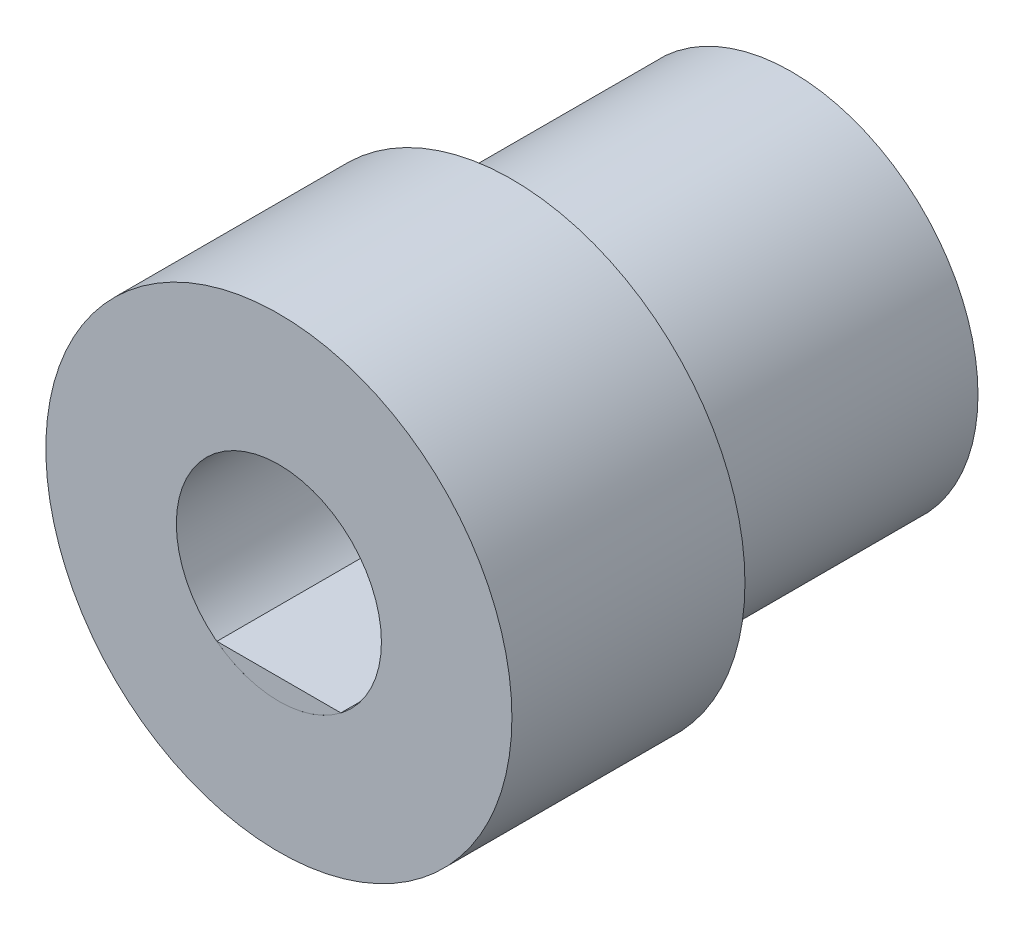
SolidWorks part; units mm, degrees
ref_plane "Plan de face" through (0, 0, 0) normal (0, 0, 1) x (1, 0, 0)
ref_plane "Plan de dessus" through (0, 0, 0) normal (0, 1, 0) x (1, 0, 0)
ref_plane "Plan de droite" through (0, 0, 0) normal (1, 0, 0) x (0, 0, -1)
sketch "Esquisse1" plane through (0, 0, 0) normal (0, 0, 1) x (1, 0, 0)
  circle A0 centre (0, 0) radius 10
  dimension "D1" = 20
extrude "Boss.-Extru.1" add sketch "Esquisse1" along normal blind 10
sketch "Esquisse2" plane through (0, 0, 0) normal (0, 0, -1) x (-1, 0, 0)
  circle A0 centre (0, 0) radius 8
  dimension "D1" = 16
extrude "Boss.-Extru.2" add sketch "Esquisse2" along normal blind 12 separate body
sketch "Esquisse3" plane through (0, 0, 10) normal (0, 0, 1) x (1, 0, 0)
  circle A0 centre (0, 0) radius 4.4
  dimension "D1" = 8.8
extrude "Enlèv. mat.-Extru.1" cut sketch "Esquisse3" against normal up to next (10 mm away)
sketch "Esquisse4" plane through (0, 0, -12) normal (0, 0, -1) x (-1, 0, 0)
  circle A0 centre (0, 0) radius 2.3
  dimension "D1" = 4.6
extrude "Enlèv. mat.-Extru.2" cut sketch "Esquisse4" against normal up to next (12 mm away)
sketch "Esquisse5" plane through (0, 0, 10) normal (0, 0, 1) x (1, 0, 0)
  line L0 (-2.6665, -3.5) -> (2.6665, -3.5)
  arc A0 (-2.6665, -3.5) -> (2.6665, -3.5) centre (0, 0) ccw
  circle A1 centre (0, 0) radius 4.4 construction
  dimension "D1" = 3.5
extrude "Boss.-Extru.3" add sketch "Esquisse5" against normal up to next separate body
sketch "Esquisse6" plane through (0, 0, -12) normal (0, 0, -1) x (-1, 0, 0)
  line L0 (-1.9621, -1.2) -> (1.9621, -1.2)
  arc A0 (1.9621, -1.2) -> (-1.9621, -1.2) centre (0, 0) cw
  circle A1 centre (0, 0) radius 2.3 construction
  dimension "D1" = 1.2
extrude "Boss.-Extru.4" add sketch "Esquisse6" against normal up to surface (12 mm away) up to face at (4.4, 0, 0)
